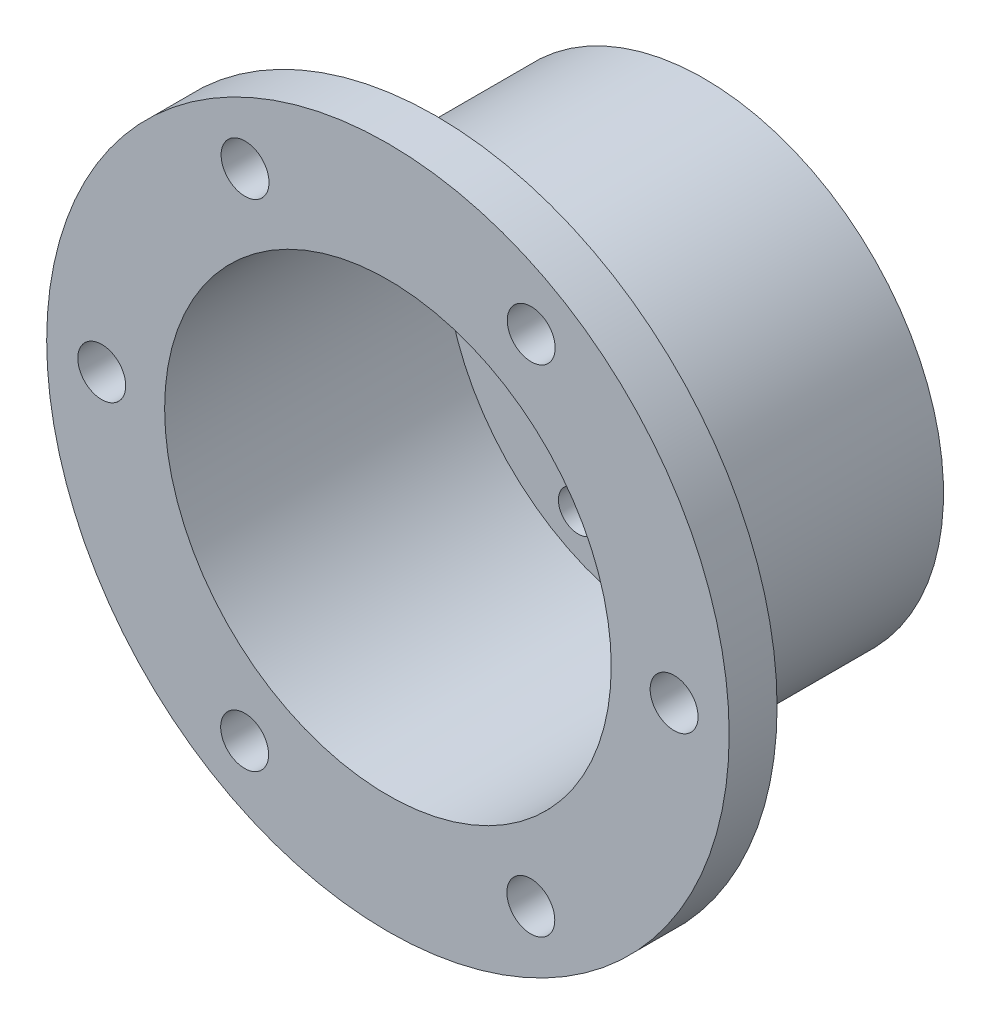
SolidWorks part; units mm, degrees
material "Resina de melamina"
ref_plane "Alzado" through (0, 0, 0) normal (0, 0, 1) x (1, 0, 0)
ref_plane "Planta" through (0, 0, 0) normal (0, 1, 0) x (1, 0, 0)
ref_plane "Vista lateral" through (0, 0, 0) normal (1, 0, 0) x (0, 0, -1)
sketch "Croquis1" plane through (0, 0, 0) normal (0, 0, 1) x (1, 0, 0)
  circle A0 centre (0, 0) radius 18.65
  circle A1 centre (0, 0) radius 21.4
  dimension "D1" = 37.3
  dimension "D2" = 42.8
extrude "Saliente-Extruir1" add sketch "Croquis1" along normal blind 26.4
sketch "Croquis2" plane through (0, 0, 0) normal (0, 0, -1) x (-1, 0, 0)
  circle A0 centre (0, 0) radius 18.65
  dimension "D1" = 37.3
extrude "Saliente-Extruir2" add sketch "Croquis2" against normal blind 3
sketch "Croquis3" plane through (0, 0, 26.4) normal (0, 0, 1) x (1, 0, 0)
  circle A0 centre (0, 0) radius 21.4
  circle A1 centre (0, 0) radius 28.5
  dimension "D1" = 57
extrude "Saliente-Extruir3" add sketch "Croquis3" against normal blind 4
sketch "Croquis4" plane through (0, 0, 0) normal (0, 0, -1) x (-1, 0, 0)
  line L0 (0, 0) -> (0, -7) construction
  line L1 (-12.848, 0.2243) -> (-13.8479, 0.2417) construction
  line L2 (-13.8479, 0.2417) -> (-17.1474, 0.2993) construction
  circle A0 centre (0, -7) radius 6.15
  circle A9 centre (-15.4976, 0.2705) radius 1.65
  circle A10 centre (-7.5145, 13.5566) radius 1.65
  circle A11 centre (7.9831, 13.2861) radius 1.65
  circle A12 centre (15.4976, -0.2705) radius 1.65
  circle A13 centre (7.5145, -13.5566) radius 1.65
  circle A14 centre (-7.9831, -13.2861) radius 1.65
  dimension "D2" = 12.3
  dimension "D6" = 15.5
  dimension "D1" = 7
  dimension "D3" = 1
  dimension "D4" = 3.3
  dimension "D5" = 6
extrude "Cortar-Extruir1" cut sketch "Croquis4" against normal blind 3
sketch "Croquis6" plane through (0, 0, 26.4) normal (0, 0, 1) x (1, 0, 0)
  line L4 (0, 0) -> (23.9, -0.0193) construction
  circle A1 centre (11.9667, 20.6884) radius 2
  circle A8 centre (23.9, -0.0193) radius 2
  circle A10 centre (-11.9333, 20.7077) radius 2
  circle A16 centre (11.9333, -20.7077) radius 2
  circle A17 centre (-11.9667, -20.6884) radius 2
  circle A18 centre (-23.9, 0.0193) radius 2
  dimension "D1" = 23.9
  dimension "D2" = 4
  dimension "D3" = 6
extrude "Cortar-Extruir2" cut sketch "Croquis6" against normal through all
sketch "Croquis7" plane through (0, 0, 0) normal (0, 0, -1) x (-1, 0, 0)
  circle A0 centre (0, 0) radius 20
  circle A1 centre (0, 0) radius 21.4
  dimension "40" = 40
extrude "Cortar-Extruir3" cut sketch "Croquis7" against normal blind 22.4
